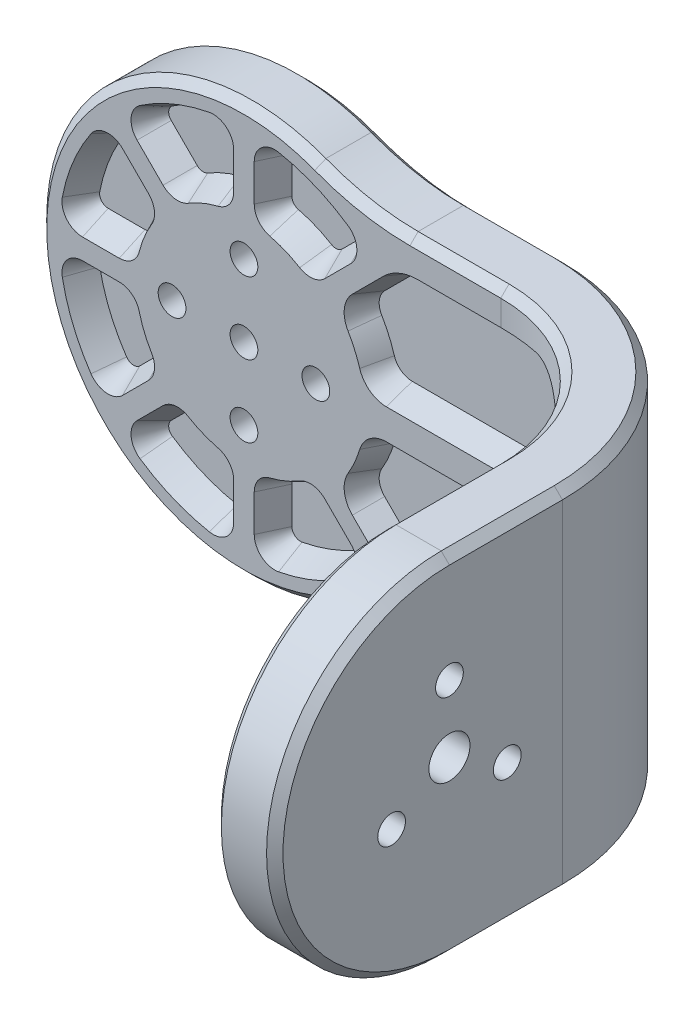
SolidWorks part; units mm, degrees
material "Bambu PLA Basic"
ref_plane "前视基准面" through (0, 0, 0) normal (0, 0, 1) x (1, 0, 0)
ref_plane "上视基准面" through (0, 0, 0) normal (0, 1, 0) x (1, 0, 0)
ref_plane "右视基准面" through (0, 0, 0) normal (1, 0, 0) x (0, 0, -1)
sketch "草图1" plane through (0, 0, 0) normal (0, 0, 1) x (1, 0, 0)
  circle A0 centre (0, 0) radius 9.85
  dimension "D1" = 19.7
extrude "凸台-拉伸1" add sketch "草图1" along normal blind 3.1
sketch "草图4" plane through (0, 0, 3.1) normal (0, 0, 1) x (1, 0, 0)
  line L1 (-5, -17) -> (45, -17)
  line L2 (-5, -17) -> (-5, 17)
  line L3 (-5, 17) -> (45, 17)
  line L4 (45, -17) -> (45, 17)
  line L5 (-5, -17) -> (45, 17) construction
  line L6 (-5, 17) -> (45, -17) construction
  circle A0 centre (0, -7) radius 1.35 construction
  circle A1 centre (0, 0) radius 1.35 construction
  circle A2 centre (7, 0) radius 1.35 construction
  circle A3 centre (0, 7) radius 1.35 construction
  circle A4 centre (-7, 0) radius 1.35 construction
  circle A5 centre (0, -7) radius 1.35 construction
  circle A6 centre (0, 0) radius 1.35 construction
  circle A7 centre (7, 0) radius 1.35 construction
  circle A8 centre (0, 7) radius 1.35 construction
  circle A9 centre (-7, 0) radius 1.35 construction
  circle A10 centre (0, 0) radius 20
  point P16 (20, 0)
  circle M2 centre (0, 0) radius 9.85
  dimension "D1" = 40
  dimension "D2" = 34
  dimension "D3" = 25
extrude "凸台-拉伸2" add sketch "草图4" along normal blind 6 contours L3 A10 L1 L2 M2 | L2 M2 | L2 M2 | L1 A10 L3 L2 M2 | A10 L1 L4 L3
sketch "草图5" plane through (0, 0, 9.1) normal (0, 0, 1) x (1, 0, 0)
  line L0 (0, 0) -> (2.907, 0) construction
  line L1 (7, 0) -> (0, 0) construction
  line L2 (0, -7) -> (0, 7) construction
  circle A3 centre (0, 0) radius 1.35 construction
  circle A5 centre (7, 0) radius 1.35
  circle A6 centre (0, -7) radius 1.35
  circle A7 centre (-7, 0) radius 1.35
  circle A8 centre (0, 0) radius 1.35
  circle A9 centre (0, 7) radius 1.35
  circle A10 centre (0, 0) radius 7 construction
  dimension "D1" = 0
extrude "切除-拉伸1" cut sketch "草图5" against normal through all
sketch "草图6" plane through (0, 0, 9.1) normal (0, 0, 1) x (1, 0, 0)
  line L0 (-2.9236, -3.8191) -> (-4.9765, -6.0098) construction
  line L1 (3.0022, 0) -> (1.5011, 2.6) construction
  line L2 (1.5011, 2.6) -> (-1.5011, 2.6) construction
  line L3 (-1.5011, 2.6) -> (-3.0022, 0) construction
  line L4 (-3.0022, 0) -> (-1.5011, -2.6) construction
  line L5 (-1.5011, -2.6) -> (1.5011, -2.6) construction
  line L6 (1.5011, -2.6) -> (3.0022, 0) construction
  line L7 (8.8829, -4.1057) -> (9.5654, -1.1821) construction
  line L8 (9.5654, -1.1821) -> (7.3747, 0.8708) construction
  line L9 (7.3747, 0.8708) -> (4.5015, 0) construction
  line L10 (4.5015, 0) -> (3.8191, -2.9236) construction
  line L11 (3.8191, -2.9236) -> (6.0098, -4.9765) construction
  line L12 (6.0098, -4.9765) -> (8.8829, -4.1057) construction
  line L13 (0, -4.5015) -> (-2.9236, -3.8191) construction
  line L14 (0.8708, -7.3747) -> (0, -4.5015) construction
  line L15 (-1.1821, -9.5654) -> (0.8708, -7.3747) construction
  line L16 (-4.1057, -8.8829) -> (-1.1821, -9.5654) construction
  line L17 (-4.9765, -6.0098) -> (-4.1057, -8.8829) construction
  line L18 (-3.8191, 2.9236) -> (-6.0098, 4.9765) construction
  line L19 (-4.5015, 0) -> (-3.8191, 2.9236) construction
  line L20 (-7.3747, -0.8708) -> (-4.5015, 0) construction
  line L21 (-9.5654, 1.1821) -> (-7.3747, -0.8708) construction
  line L22 (-8.8829, 4.1057) -> (-9.5654, 1.1821) construction
  line L23 (-6.0098, 4.9765) -> (-8.8829, 4.1057) construction
  line L24 (2.9236, 3.8191) -> (4.9765, 6.0098) construction
  line L25 (0, 4.5015) -> (2.9236, 3.8191) construction
  line L26 (-0.8708, 7.3747) -> (0, 4.5015) construction
  line L27 (1.1821, 9.5654) -> (-0.8708, 7.3747) construction
  line L28 (4.1057, 8.8829) -> (1.1821, 9.5654) construction
  line L29 (4.9765, 6.0098) -> (4.1057, 8.8829) construction
  line L30 (0, 0) -> (-12.7279, 12.7279) construction
  line L31 (-13.4154, 12.0012) -> (-8.098, 6.6838)
  line L32 (-12.0012, 13.4154) -> (-6.6838, 8.098)
  line L33 (1, 17.9722) -> (1, 10.4523)
  line L34 (-1, 17.9722) -> (-1, 10.4523)
  line L35 (14.4343, 15) -> (7.1364, 7.7021)
  line L36 (12.0012, 13.4154) -> (6.6838, 8.098)
  line L37 (10.4981, 0.2) -> (33, 0.2)
  line L38 (33, 0.2) -> (33, -0.2)
  line L39 (12.0012, -13.4154) -> (6.6838, -8.098)
  line L40 (14.4343, -15) -> (7.1364, -7.7021)
  line L41 (-1, -17.9722) -> (-1, -10.4523)
  line L42 (1, -17.9722) -> (1, -10.4523)
  line L43 (-13.4154, -12.0012) -> (-8.098, -6.6838)
  line L44 (-12.0012, -13.4154) -> (-6.6838, -8.098)
  line L45 (-17.9722, 1) -> (-10.4523, 1)
  line L46 (-17.9722, -1) -> (-10.4523, -1)
  line L47 (33, -15) -> (9.9499, -15)
  line L48 (10.5357, -17) -> (45, -17) construction
  line L49 (45, -17) -> (45, 17) construction
  line L50 (-4.5015, 0) -> (28.7518, 0) construction
  line L51 (33, 15) -> (9.9499, 15)
  line L52 (12.0012, 13.4154) -> (13.5858, 15)
  line L54 (33, 15) -> (33, -15)
  line L55 (33, -0.2) -> (10.4981, -0.2)
  line L57 (12.0012, -13.4154) -> (13.5858, -15)
  line L59 (17.9722, -1) -> (10.4523, -1) [skipped]
  line L60 (17.9722, 1) -> (10.4523, 1) [skipped]
  line L61 (13.4154, -12.0012) -> (8.098, -6.6838) [skipped]
  line L62 (13.4154, 12.0012) -> (8.098, 6.6838) [skipped]
  circle A0 centre (0, 0) radius 2.6 construction
  circle A2 centre (0, 0) radius 10.5
  arc A3 (9.9499, 15) -> (9.9499, -15) centre (0, 0) ccw
  arc A4 (10.5357, 17) -> (10.5357, -17) centre (0, 0) ccw construction
  arc A5 (9.9499, -15) -> (12.0012, -13.4154) centre (0, 0) ccw
  arc A6 (12.0012, 13.4154) -> (9.9499, 15) centre (0, 0) ccw
  point P76 (0, 0)
  dimension "D4" = 21
  dimension "D5" = 2
  dimension "D1" = 5.2
  dimension "D2" = 5.2
  dimension "D3" = 4
  dimension "D6" = 45
  dimension "D7" = 1
  dimension "D9" = 2
  dimension "D10" = 12
  dimension "D11" = 0.2
  dimension "D12" = 0.2
  dimension "D13" = 0.6
  dimension "D8" = 8
extrude "切除-拉伸2" cut sketch "草图6" against normal blind 2.5
fillet "圆角1" radius 2 24 edges at (-1, 17.9722, 7.85) (-1, 10.4523, 7.85) (-6.6838, 8.098, 7.85) (-12.0012, 13.4154, 7.85) (12.0012, -13.4154, 7.85) (1, -17.9722, 7.85) (1, -10.4523, 7.85) (6.6838, -8.098, 7.85) (-12.0012, -13.4154, 7.85) (-6.6838, -8.098, 7.85) (-1, -10.4523, 7.85) (-1, -17.9722, 7.85) (-17.9722, -1, 7.85) (-10.4523, -1, 7.85) (-8.098, -6.6838, 7.85) (-13.4154, -12.0012, 7.85) (-13.4154, 12.0012, 7.85) (-8.098, 6.6838, 7.85) (-10.4523, 1, 7.85) (-17.9722, 1, 7.85) (12.0012, 13.4154, 7.85) (6.6838, 8.098, 7.85) (1, 10.4523, 7.85) (1, 17.9722, 7.85)
fillet "圆角2" radius 6 2 edges at (14.4343, 15, 7.85) (14.4343, -15, 7.85)
fillet "圆角5" radius 4 8 edges at (33, 15, 7.85) (33, -15, 7.85) (7.1364, -7.7021, 7.85) (7.1364, 7.7021, 7.85) (10.4981, 0.2, 7.85) (10.4981, -0.2, 7.85) (33, -0.2, 7.85) (33, 0.2, 7.85)
fillet "圆角3" radius 25 2 edges at (10.5357, -17, 6.1) (10.5357, 17, 6.1)
sketch "草图7" plane through (0, 0, 9.1) normal (0, 0, 1) x (1, 0, 0)
  line L0 (16.1555, -17) -> (45, -17) construction
  line L1 (45, 17) -> (39, 17)
  line L2 (45, 17) -> (45, -17)
  line L3 (45, -17) -> (39, -17)
  line L4 (39, 17) -> (39, -17)
  dimension "D1" = 6
extrude "凸台-拉伸3" add sketch "草图7" along normal blind 42
sketch "草图8" plane through (39, 0, 0) normal (-1, 0, 0) x (0, 0, 1)
  line L0 (51.1, 17) -> (51.1, -17) construction
  line L1 (51.1, 17) -> (9.1, 17) construction
  line L2 (51.1, -17) -> (9.1, -17) construction
  line L3 (34.1, 17) -> (76.286, 27.6609)
  line L4 (76.286, 27.6609) -> (73.9848, -34.5768)
  line L5 (73.9848, -34.5768) -> (34.1, -17)
  arc A0 (34.1, -17) -> (34.1, 17) centre (34.1, 0) ccw
extrude "切除-拉伸3" cut sketch "草图8" against normal through all
chamfer "倒角2" distance 6 angle 20 20 edges at (33, 7.6, 6.6) (9.6122, 4.2256, 6.6) (22.9598, 15, 6.6) (9.6122, -4.2256, 6.6) (33, -7.6, 6.6) (31.8284, -13.8284, 6.6) (22.9598, -15, 6.6) (31.8284, 13.8284, 6.6) (11.1631, -11.7288, 6.6) (21.4392, -0.2, 6.6) (21.4392, 0.2, 6.6) (11.1631, 11.7288, 6.6) (14.6235, 14.5433, 6.6) (31.8284, 1.3716, 6.6) (11.4945, 0.988, 6.6) (8.509, 7.8869, 6.6) (11.4945, -0.988, 6.6) (31.8284, -1.3716, 6.6) (14.6235, -14.5433, 6.6) (8.509, -7.8869, 6.6)
fillet "圆角4" radius 14 1 edges at (39, 0, 9.1)
fillet "圆角6" radius 20 1 edges at (45, 0, 3.1)
chamfer "倒角1" distance 2.5 angle 25 96 edges at (-1, -13.9254, 6.6) (-1, -12.1347, 7.85) (-1, -15.7162, 7.85) (-6.8883, -16.6298, 6.6) (-10.1157, -14.8887, 7.85) (-3.375, -17.6808, 7.85) (-9.1397, -10.5539, 6.6) (-4.0182, -9.7007, 6.6) (-10.9828, -13.4227, 6.6) (-6.701, -8.7165, 6.6) (-1.4252, -10.9018, 6.6) (-1.7252, -17.2573, 6.6) (-5.4257, -8.9895, 7.85) (-2.52, -10.1931, 7.85) (-10.4059, -11.8202, 7.85) (-7.8734, -9.2876, 7.85) (-10.5539, -9.1397, 6.6) (-9.2876, -7.8734, 7.85) (-11.8202, -10.4059, 7.85) (-16.6298, -6.8883, 6.6) (-17.6808, -3.375, 7.85) (-14.8887, -10.1157, 7.85) (-13.9254, -1, 6.6) (-9.7007, -4.0182, 6.6) (-17.2573, -1.7252, 6.6) (-10.9018, -1.4252, 6.6) (-8.7165, -6.701, 6.6) (-13.4227, -10.9828, 6.6) (-10.1931, -2.52, 7.85) (-8.9895, -5.4257, 7.85) (-15.7162, -1, 7.85) (-12.1347, -1, 7.85) (-13.9254, 1, 6.6) (-12.1347, 1, 7.85) (-15.7162, 1, 7.85) (-16.6298, 6.8883, 6.6) (-14.8887, 10.1157, 7.85) (-17.6808, 3.375, 7.85) (-10.5539, 9.1397, 6.6) (-9.7007, 4.0182, 6.6) (-13.4227, 10.9828, 6.6) (-8.7165, 6.701, 6.6) (-10.9018, 1.4252, 6.6) (-17.2573, 1.7252, 6.6) (-8.9895, 5.4257, 7.85) (-10.1931, 2.52, 7.85) (-11.8202, 10.4059, 7.85) (-9.2876, 7.8734, 7.85) (1, 13.9254, 6.6) (1, 12.1347, 7.85) (1, 15.7162, 7.85) (6.8883, 16.6298, 6.6) (10.1157, 14.8887, 7.85) (3.375, 17.6808, 7.85) (9.1397, 10.5539, 6.6) (4.0182, 9.7007, 6.6) (10.9828, 13.4227, 6.6) (6.701, 8.7165, 6.6) (1.4252, 10.9018, 6.6) (1.7252, 17.2573, 6.6) (5.4257, 8.9895, 7.85) (2.52, 10.1931, 7.85) (10.4059, 11.8202, 7.85) (7.8734, 9.2876, 7.85) (-9.1397, 10.5539, 6.6) (-7.8734, 9.2876, 7.85) (-10.4059, 11.8202, 7.85) (-6.8883, 16.6298, 6.6) (-3.375, 17.6808, 7.85) (-10.1157, 14.8887, 7.85) (-1, 13.9254, 6.6) (-4.0182, 9.7007, 6.6) (-1.7252, 17.2573, 6.6) (-1.4252, 10.9018, 6.6) (-6.701, 8.7165, 6.6) (-10.9828, 13.4227, 6.6) (-2.52, 10.1931, 7.85) (-5.4257, 8.9895, 7.85) (-1, 15.7162, 7.85) (-1, 12.1347, 7.85) (4.0182, -9.7007, 6.6) (2.52, -10.1931, 7.85) (5.4257, -8.9895, 7.85) (9.1397, -10.5539, 6.6) (10.4059, -11.8202, 7.85) (7.8734, -9.2876, 7.85) (6.8883, -16.6298, 6.6) (1, -13.9254, 6.6) (10.9828, -13.4227, 6.6) (1.7252, -17.2573, 6.6) (1.4252, -10.9018, 6.6) (6.701, -8.7165, 6.6) (1, -15.7162, 7.85) (1, -12.1347, 7.85) (10.1157, -14.8887, 7.85) (3.375, -17.6808, 7.85)
sketch "草图9" plane through (39, 0, 0) normal (-1, 0, 0) x (0, 0, 1)
  circle A0 centre (34.1, 0) radius 2
  dimension "D1" = 4
extrude "切除-拉伸4" cut sketch "草图9" against normal through all
sketch "草图10" plane through (39, 0, 0) normal (-1, 0, 0) x (0, 0, 1)
  circle A0 centre (34.1, 0) radius 6.5 construction
  circle A1 centre (34.1, 6.5) radius 1.35
  circle A3 centre (39.7292, -3.25) radius 1.35
  circle A4 centre (28.4708, -3.25) radius 1.35
  dimension "D1" = 13
  dimension "D2" = 2.7
  dimension "D3" = 3
extrude "切除-拉伸5" cut sketch "草图10" against normal blind 10
chamfer "倒角3" distance 0.8 angle 45 20 edges at (11.5911, -17.4202, 9.1) (20.5777, -17, 9.1) (-20, 0, 9.1) (34.8995, -17, 13.2005) (11.5911, 17.4202, 9.1) (39, -17, 28.6) (20.5777, 17, 9.1) (39, 0, 51.1) (34.8995, 17, 13.2005) (39, 17, 28.6) (20.5777, -17, 3.1) (39.1421, -17, 8.9579) (11.5911, -17.4202, 3.1) (45, -17, 28.6) (-20, 0, 3.1) (45, 0, 51.1) (11.5911, 17.4202, 3.1) (45, 17, 28.6) (20.5777, 17, 3.1) (39.1421, 17, 8.9579)
